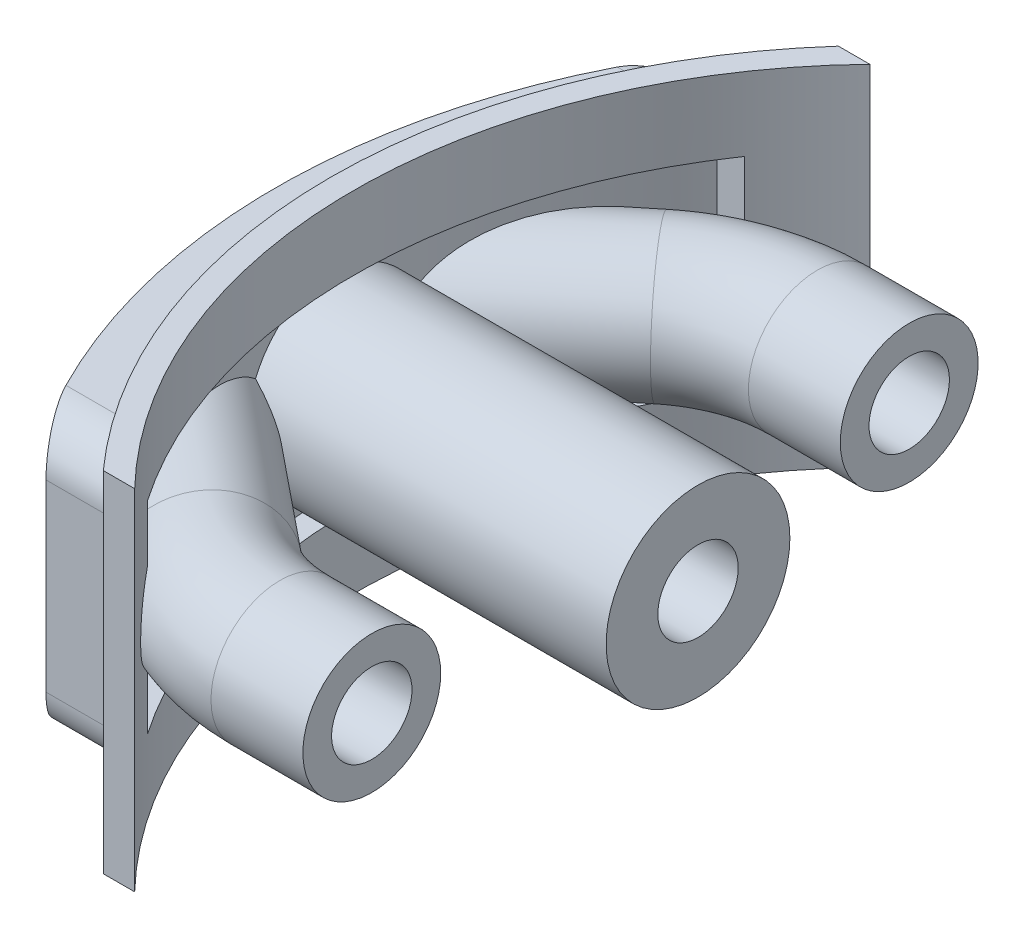
SolidWorks part; units mm, degrees
ref_plane "Front Plane" through (0, 0, 0) normal (0, 0, 1) x (1, 0, 0)
ref_plane "Top Plane" through (0, 0, 0) normal (0, 1, 0) x (1, 0, 0)
ref_plane "Right Plane" through (0, 0, 0) normal (1, 0, 0) x (0, 0, -1)
sketch "Sketch1" plane through (0, 0, 0) normal (0, 1, 0) x (1, 0, 0)
  line L0 (-71.0633, 44.45) -> (-61.8921, 44.45)
  line L1 (-71.0633, -44.45) -> (-61.8921, -44.45)
  line L2 (0, 0) -> (-76.2, 0) construction
  arc A0 (-71.0633, 44.45) -> (-71.0633, -44.45) centre (0, 0) ccw
  arc A1 (-61.8921, 44.45) -> (-61.8921, -44.45) centre (0, 0) ccw
  dimension "D1" = 167.64
  dimension "D2" = 152.4
  dimension "D3" = 88.9
extrude "Boss-Extrude1" add sketch "Sketch1" along normal blind 19.05 and the other way blind 19.05
sketch "Sketch14" plane through (0, 0, 0) normal (1, 0, 0) x (0, 0, -1)
  line L0 (-44.45, -19.05) -> (-44.45, 19.05) construction
  line L1 (-50.8, 24.13) -> (50.8, 24.13)
  line L2 (-50.8, 24.13) -> (-50.8, 13.97)
  line L3 (-50.8, 13.97) -> (50.8, 13.97)
  line L4 (50.8, 24.13) -> (50.8, 13.97)
  line L5 (44.45, -19.05) -> (44.45, 19.05) construction
  line L6 (-50.8, 19.05) -> (50.8, 19.05) construction
  line L7 (44.45, 19.05) -> (-44.45, 19.05) construction
  line L8 (-49.7824, 0) -> (49.7824, 0) construction
  line L9 (-50.8, -19.05) -> (50.8, -19.05) construction
  line L10 (50.8, -24.13) -> (50.8, -13.97)
  line L11 (-50.8, -13.97) -> (50.8, -13.97)
  line L12 (-50.8, -24.13) -> (-50.8, -13.97)
  line L13 (-50.8, -24.13) -> (50.8, -24.13)
  dimension "D1" = 10.16
  dimension "D2" = 6.35
  dimension "D3" = 6.35
extrude "Boss-Extrude11" add sketch "Sketch14" against normal up to surface (5.9961 mm away) from offset 50.8 up to face at (-69.0461, 0, 0) offset against normal yes
sketch "Sketch15" plane through (0, 24.13, 0) normal (0, 1, 0) x (1, 0, 0)
  line L0 (-51.6365, -51.6365) -> (-53.8815, -53.8815)
  line L1 (-53.8815, 53.8815) -> (-51.6365, 51.6365)
  line L2 (0, 0) -> (-123.1347, 0) construction
  arc A0 (-51.6365, 51.6365) -> (-51.6365, -51.6365) centre (0, 0) ccw
  arc A1 (-56.7961, 50.8) -> (-56.7961, -50.8) centre (0, 0) ccw construction
  arc A2 (-53.8815, -53.8815) -> (-53.8815, 53.8815) centre (0, 0) ccw
  dimension "D1" = 146.05
  dimension "D2" = 90
extrude "Cut-Extrude1" cut sketch "Sketch15" against normal up to next
sketch "Sketch17" plane through (0, 13.97, 0) normal (0, -1, 0) x (1, 0, 0)
  line L0 (-64.0532, 41.275) -> (-60.2414, 41.275)
  line L1 (-56.7961, 50.8) -> (-52.4596, 50.8) construction
  line L3 (-52.4596, 50.8) -> (-56.7961, 50.8)
  arc A0 (-61.8921, 44.45) -> (-61.8921, -44.45) centre (0, 0) ccw construction
  arc A1 (-52.4596, 50.8) -> (-52.4596, -50.8) centre (0, 0) ccw construction
  arc A2 (-52.4596, 50.8) -> (-60.2414, 41.275) centre (0, 0) ccw
  arc A4 (-64.0532, 41.275) -> (-56.7961, 50.8) centre (0, 0) cw
  dimension "D1" = 9.525
extrude "Boss-Extrude12" add sketch "Sketch17" along normal up to surface (27.94 mm away) up to face at (-58.909, -13.97, 0)
mirror "Mirror4" about plane through (0, 0, 0) normal (0, 1, 0) of "Cut-Extrude1"
sketch "Sketch2" plane through (0, 0, 0) normal (1, 0, 0) x (0, 0, -1)
  circle A0 centre (0, 0) radius 12.7
  dimension "D1" = 25.4
extrude "Boss-Extrude2" add sketch "Sketch2" against normal up to surface (49.7342 mm away) from offset 25.4 up to face at (-69.5742, 0, -1.7539) offset against normal yes
ref_axis "Axis1" through (0, -13.97, 0) along (0, 1, 0)
sketch "Sketch6" plane through (0, 0, 0) normal (0, 1, 0) x (1, 0, 0)
  line L0 (0, 0) -> (-83.82, 0) construction
  line L1 (-25.4, 5.5562) -> (-48.7517, 5.5562)
  line L2 (-25.4, -12.7) -> (-25.4, 12.7) construction
  line L3 (-55.1017, 3.8548) -> (-59.7829, 1.1521)
  line L4 (-60.2909, 0) -> (-60.2909, 1.016) construction
  line L5 (-60.6853, 1.0679) -> (-83.5116, 7.1842)
  line L6 (-25.4, 5.5562) -> (-25.4, 0)
  line L7 (-25.4, 0) -> (-83.82, 0)
  line L8 (-83.82, 0) -> (-83.82, 7.1842)
  line L9 (-83.82, 7.1842) -> (-83.5116, 7.1842)
  arc A0 (-71.0633, 44.45) -> (-71.0633, -44.45) centre (0, 0) ccw construction
  arc A1 (-60.2909, 1.016) -> (-59.7829, 1.1521) centre (-60.2909, 2.032) ccw
  arc A2 (-60.6853, 1.0679) -> (-60.2909, 1.016) centre (-60.2909, 2.54) ccw
  arc A3 (-48.7517, 5.5562) -> (-55.1017, 3.8548) centre (-48.7517, -7.1438) ccw
  dimension "D2" = 1.016
  dimension "D3" = 1.524
  dimension "D7" = 12.7
  dimension "D1" = 1.016
  dimension "D4" = 15
  dimension "D5" = 7.1842
  dimension "D6" = 5.5562
  dimension "D8" = 30
revolve "Cut-Revolve1" cut sketch "Sketch6" angle 360 about L0
ref_plane "Plane3" through (0, 0, 0) normal (-0.7771, 0, -0.6293) x (-0.6293, 0, 0.7771)
sketch "Sketch7" plane through (0, 0, 0) normal (-0.7771, 0, -0.6293) x (-0.6293, 0, 0.7771)
  line L0 (0, -13.97) -> (0, 13.97) construction
  circle A0 centre (63.5, 0) radius 9.525
  dimension "D1" = 19.05
  dimension "D2" = 63.5
extrude "Boss-Extrude4" add sketch "Sketch7" along normal up to surface (0.1767 mm away) from offset 21.59 up to face at (-75.1836, -2.7246, 12.4043)
sketch "Sketch10" plane through (0, 0, 0) normal (0, 1, 0) x (1, 0, 0)
  line L0 (-62.0318, -31.4769) -> (-82.482, -14.9166) construction
  line L1 (-50.7461, -28.3594) -> (-70.0839, -12.7) construction
  line L2 (-58.5351, -27.1589) -> (-57.2479, -28.2012) construction
  line L3 (-61.205, -41.275) -> (-50.7461, -28.3594) construction
  line L5 (-66.5275, -24.3286) -> (-68.8849, -24.3286)
  line L6 (-69.5243, -24.1022) -> (-70.1637, -24.8918) construction
  line L7 (-68.5652, -22.9178) -> (-69.5243, -24.1022) construction
  line L8 (-83.6884, -4.6954) -> (-69.7982, -23.8136)
  line L9 (-83.6884, -4.6954) -> (-88.2096, -10.2785)
  line L10 (-88.2096, -10.2785) -> (-62.0318, -31.4769)
  line L16 (-50.7461, -28.3594) -> (-70.0839, -12.7) construction
  line L23 (-56.7404, -35.7617) -> (-82.482, -14.9166) construction
  line L32 (-50.7461, -28.3594) -> (-70.0839, -12.7) construction
  line L39 (-58.5351, -27.1589) -> (-62.0318, -31.4769)
  arc A0 (-71.0633, 44.45) -> (-71.0633, -44.45) centre (0, 0) ccw construction
  arc A1 (-69.5243, -24.1022) -> (-68.8849, -24.3286) centre (-68.8849, -23.3126) ccw
  arc A2 (-69.7982, -23.8136) -> (-69.5243, -24.1022) centre (-68.5652, -22.9178) ccw
  arc A3 (-58.5351, -27.1589) -> (-66.5275, -24.3286) centre (-66.5275, -37.0286) ccw
  dimension "D2" = 1.016
  dimension "D3" = 1.524
  dimension "D7" = 12.7
  dimension "D1" = 1.016
  dimension "D4" = 15
  dimension "D5" = 7.1842
  dimension "D6" = 5.5562
  dimension "D9" = 63.5
revolve "Cut-Revolve2" cut sketch "Sketch10" angle 360 about L10
sketch "Sketch8" plane through (0, 0, 0) normal (0, 1, 0) x (1, 0, 0)
  line L2 (-46.047, -37.1374) -> (-33.347, -37.1374)
  line L3 (-50.7461, -28.3594) -> (-59.3473, -38.9809) construction
  line L4 (-62.0318, -31.4769) -> (-50.5595, -40.767) construction
  line L5 (-58.5351, -27.1589) -> (-65.5284, -35.7949) construction
  line L6 (-61.205, -41.275) -> (-50.7461, -28.3594) construction
  arc A0 (-62.0318, -31.4769) -> (-46.047, -37.1374) centre (-46.047, -11.7374) ccw
  dimension "D1" = 25.4
  dimension "D2" = 12.7
sketch "Sketch18" plane through (0, 0, 0) normal (0, 1, 0) x (1, 0, 0)
  line L0 (-56.0375, -24.0746) -> (-66.5694, -37.0804)
  line L11 (-50.7461, -28.3594) -> (-70.0839, -12.7) construction
  line L18 (-56.0375, -24.0746) -> (-50.7461, -28.3594)
  line L19 (-50.7461, -28.3594) -> (-61.205, -41.275)
  line L20 (-58.5351, -27.1589) -> (-65.5284, -35.7949) construction
  line L21 (-61.205, -41.275) -> (-64.0532, -41.275)
  line L22 (-60.2414, -41.275) -> (-64.0532, -41.275) construction
  arc A0 (-61.8921, 44.45) -> (-61.8921, -44.45) centre (0, 0) ccw construction
  arc A1 (-66.5694, -37.0804) -> (-64.0532, -41.275) centre (0, 0) ccw
  arc A2 (-56.7961, 50.8) -> (-56.7961, -50.8) centre (0, 0) ccw construction
extrude "Cut-Extrude2" cut sketch "Sketch18" against normal up to surface and the other way up to surface up to face at (-65.2969, 0.0854, 28.2891) other way up to face at (-65.2969, 0.0854, 28.2891)
sketch "Sketch11" plane through (-22.0699, 0, -17.8719) normal (0.7771, 0, 0.6293) x (0.6293, 0, -0.7771)
  circle A1 centre (-63.5, 0) radius 5.5563
  circle A2 centre (-63.5, 0) radius 9.525
  arc A3 (-70.7104, -6.2238) -> (-70.7104, 6.2238) centre (-63.5, 0) ccw construction
  circle A4 centre (-63.5, 0) radius 5.5563 construction
sweep "Sweep2" add profiles "Sketch11" path "Sketch8"
mirror "Mirror1" about plane through (0, 0, 0) normal (0, 0, 1) of "Boss-Extrude4", "Cut-Revolve2", "Boss-Extrude12", "Sweep2", "Cut-Extrude2"
fillet "Fillet2" radius 6.35 4 edges at (-66.4777, -19.05, 44.45) (-66.4777, 19.05, 44.45) (-66.4777, 19.05, -44.45) (-66.4777, -19.05, -44.45)
equation "\"D2@Sketch6\"=\"D1@Sketch6\""
equation "\"D3@Sketch6\"=1.5*\"D1@Sketch6\""
equation "\"D5@Sketch6\"  = \"D1@Sketch6\" * ( \"ER_pitch\" ) ^ .5"
equation "\"D2@Sketch10\"=\"D1@Sketch10\""
equation "\"D3@Sketch10\"=1.5*\"D1@Sketch10\""
equation "\"D5@Sketch10\" = \"D1@Sketch10\" * ( \"ER_roll\" ) ^ .5"
equation "\"ER_roll\"= 50"
equation "\"ER_pitch\"= 50"
